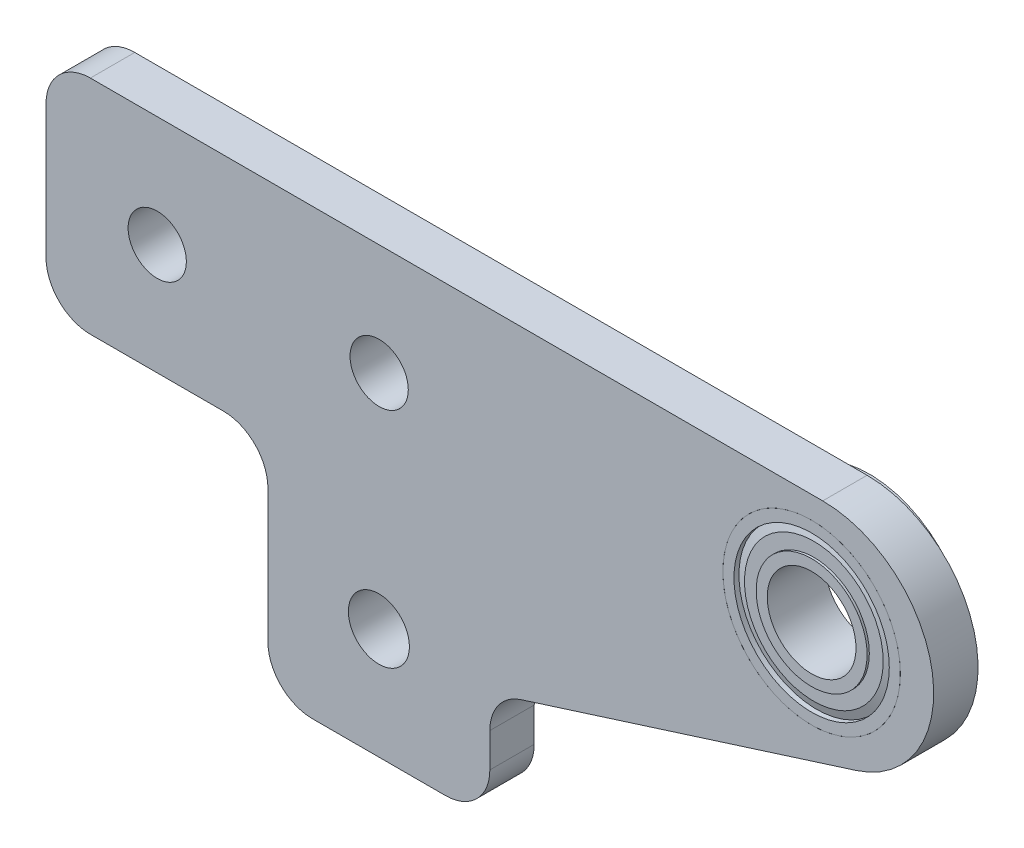
SolidWorks part; units mm, degrees
ref_plane "Front Plane" through (0, 0, 0) normal (0, 0, 1) x (1, 0, 0)
ref_plane "Top Plane" through (0, 0, 0) normal (0, 1, 0) x (1, 0, 0)
ref_plane "Right Plane" through (0, 0, 0) normal (1, 0, 0) x (0, 0, -1)
sketch "Sketch1" plane through (0, 0, 0) normal (0, 0, 1) x (1, 0, 0)
  line L0 (1, 10) -> (-69, 10)
  line L1 (-69, 10) -> (-69, -10)
  line L2 (-69, -10) -> (-49, -10)
  line L3 (-49, -10) -> (-49, -30)
  line L4 (-49, -30) -> (-29, -30)
  line L5 (-29, -30) -> (-29, -20)
  line L6 (-29, -20) -> (4.0217, -9.5325)
  line L7 (0, 0) -> (1, 0) construction
  circle A0 centre (0, 0) radius 8
  circle A1 centre (1, 0) radius 10
  dimension "D1" = 16
  dimension "D2" = 20
  dimension "D3" = 80
  dimension "D4" = 20
  dimension "D5" = 20
  dimension "D6" = 20
  dimension "D7" = 10
  dimension "D8" = 20
  dimension "D9" = 1
extrude "Boss-Extrude1" add sketch "Sketch1" along normal mid plane 4 contours A1 L0 L1 L2 L3 L4 L5 L6 | A1 A0 region at (-36.4319, -5.6111, 0) region at (7.8711, 6.8711, 0)
sketch "Sketch2" plane through (0, 0, 2) normal (0, 0, 1) x (1, 0, 0)
  line L0 (-69, 0) -> (-58.975, 0) construction
  line L1 (-69, 10) -> (-69, -10) construction
  line L2 (-58.975, 0) -> (-38.975, 0) construction
  line L3 (-39, -30) -> (-39, -20) construction
  line L4 (-49, -30) -> (-29, -30) construction
  circle A0 centre (-39, -20) radius 2.75
  circle A1 centre (-58.975, 0) radius 2.625
  circle A2 centre (-38.975, 0) radius 2.625
  dimension "D1" = 5.5
  dimension "D2" = 5.25
  dimension "D4" = 20
  dimension "D3" = 10
  dimension "D5" = 7.4
extrude "Cut-Extrude1" cut sketch "Sketch2" against normal through all
fillet "Fillet1" radius 4 6 edges at (-29, -20, 0) (-29, -30, 0) (-49, -30, 0) (-49, -10, 0) (-69, -10, 0) (-69, 10, 0)
sketch "Sketch3" plane through (0, 0, -2) normal (0, 0, -1) x (-1, 0, 0)
  circle A0 centre (0, 0) radius 9
  dimension "D1" = 18
extrude "Boss-Extrude2" add sketch "Sketch3" along normal blind 1.2 separate body
sketch "Sketch4" plane through (0, 0, -2) normal (0, 0, 1) x (1, 0, 0)
  circle A0 centre (0, 0) radius 8 construction
  circle A1 centre (0, 0) radius 8
extrude "Boss-Extrude3" add sketch "Sketch4" along normal up to surface (4 mm away) up to face at (-36.25, -20, 2)
sketch "Sketch5" plane through (0, 0, 2) normal (0, 0, 1) x (1, 0, 0)
  circle A0 centre (0, 0) radius 4
  circle A1 centre (0, 0) radius 5
  circle A2 centre (0, 0) radius 7
  dimension "D1" = 8
  dimension "D2" = 10
  dimension "D3" = 14
extrude "Cut-Extrude2" cut sketch "Sketch5" against normal through all contours A0 region at (0, 0, 2)
extrude "Cut-Extrude3" cut sketch "Sketch5<3>" against normal blind 0.2 contours A2 A1 region at (-6.802, 0, 2)
sketch "Sketch5<3>" plane through (0, 0, 2) normal (0, 0, 1) x (1, 0, 0) same geometry as "Sketch5"
ref_plane "Plane2" through (0, 0, -0.6) normal (0, 0, 1) x (1, 0, 0)
mirror "Mirror8" about plane through (0, 0, -0.6) normal (0, 0, 1) of "Cut-Extrude3"
ref_plane "Plane1" through (0, 0, 0) normal (1, 0, 0) x (0, 0, -1)
sketch "Sketch6" plane through (0, 0, 0) normal (1, 0, 0) x (0, 0, -1)
  line L0 (-1.8, 6.25) -> (-1.55, 7)
  line L1 (-1.8, 7) -> (-1.8, -7) construction
  line L2 (-1.55, 7) -> (-1.8, 7)
  line L3 (-1.8, 7) -> (-1.8, 6.25)
  line L4 (-2, 8) -> (3.2, 8) construction
  line L5 (3.2, -9) -> (3.2, 9) construction
  line L6 (0.6, 8) -> (0.6, 5.0945) construction
  line L7 (3, 6.25) -> (2.75, 7)
  line L8 (3, 7) -> (3, 6.25)
  line L9 (2.75, 7) -> (3, 7)
  dimension "D1" = 0.25
  dimension "D2" = 0.75
revolve "Cut-Revolve1" cut sketch "Sketch6" angle 360 about axis through (0, 0, 2) along (0, 0, -1)
move or copy body "Body-Move/Copy1" [suppressed] bodies to move or copy 102 107
